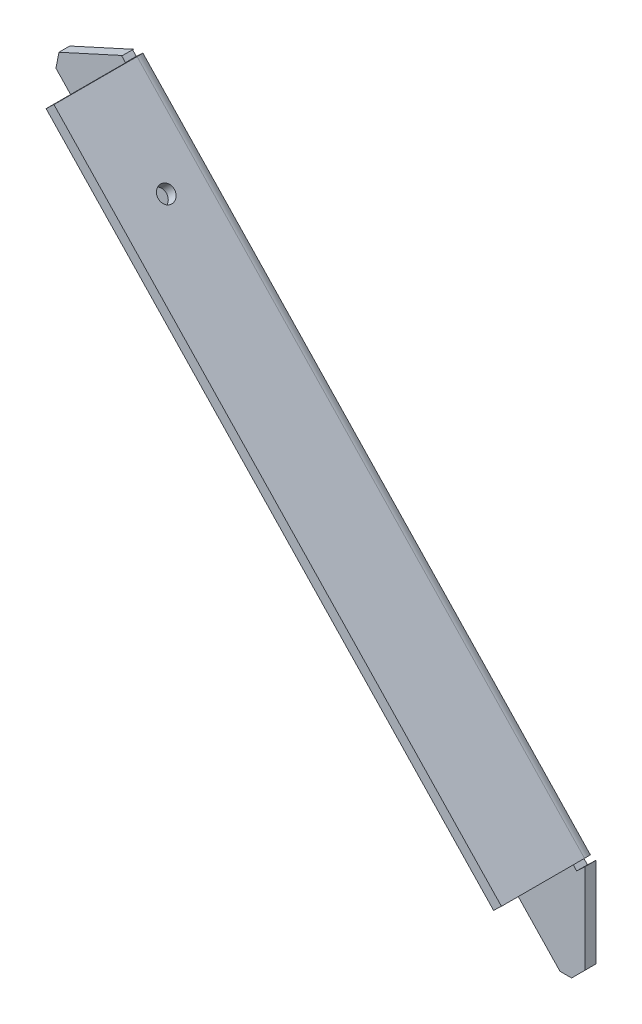
SolidWorks part; units mm, degrees
note: The reader was unsure of these and kept them because the rebuilt part matched: flange length of "Edge-Flange1".
material "ASTM A36 Steel"
ref_plane "Front Plane" through (0, 0, 0) normal (0, 0, 1) x (1, 0, 0)
ref_plane "Top Plane" through (0, 0, 0) normal (0, 1, 0) x (1, 0, 0)
ref_plane "Right Plane" through (0, 0, 0) normal (1, 0, 0) x (0, 0, -1)
sketch "Sketch1" plane through (0, 0, 0) normal (0, 0, 1) x (1, 0, 0)
  line L0 (88.2179, -94.9528) -> (-98.5073, 101.4158)
  line L1 (97.5288, -53.9528) -> (-68.2572, 120.3951)
  line L2 (88.2179, -94.9528) -> (92.5288, -94.9528)
  line L3 (-68.2572, 120.3951) -> (-97.403, 107.1127)
  line L4 (97.5288, -89.9528) -> (97.5288, -53.9528)
  line L5 (92.5288, -94.9528) -> (97.5288, -89.9528)
  line L6 (-98.5073, 101.4158) -> (-97.403, 107.1127)
base flange "Base-Flange1" sketch "Sketch1" thickness 4 reverse thickness direction no parameters "D1"=0.2
edge flange "Edge-Flange1" sketch "Sketch8" flange angle 90 flange length 35 flange position material inside bend radius 0.2 thickness 4 relief rectangular parameters "D6"=10
sketch "Sketch8" plane through (24.2756, 23.0835, 0) normal (0.7247, 0.6891, 0) x (-0.6891, 0.7247, 0)
  line L0 (-106.3044, 0) -> (134.2829, 0) construction
  line L1 (-106.3044, 0) -> (134.2829, 0)
  line L2 (-106.3044, 0) -> (-106.3044, 31)
  line L3 (-106.3044, 31) -> (134.2829, 31)
  line L4 (134.2829, 31) -> (134.2829, 0)
bend "EdgeBend1" bend radius 0.2 bend angle 90 parameters "D5"=1
sketch "Sketch9" plane through (24.2756, 23.0835, 0) normal (0.7247, 0.6891, 0) x (0, 0, -1)
  line L0 (-0.2, 134.2829) -> (-31, 134.2829) construction
  line L1 (-31, 134.2829) -> (-31, -106.3044) construction
  circle A0 centre (-13.5, 99.2829) radius 3
  dimension "D1" = 6
  dimension "D2" = 35
  dimension "D3" = 17.5
extrude "Cut-Extrude1" cut sketch "Sketch9" against normal blind 10 normal cut yes
sketch "Bend-Lines1" [suppressed] plane through (0, 0, 0) normal (0, 1, 0) x (1, 0, 0)
sketch "Bounding-Box1" [suppressed] plane through (0, 0, 0) normal (0, 1, 0) x (1, 0, 0)
sheet metal parameters "Sheet-Metal1" thickness 4 parameters "D1"=0.2
flat pattern "Flat-Pattern1" [suppressed]
sketch "Bend-Lines2" plane through (0, 0, 0) normal (0, 1, 0) x (1, 0, 0)
sketch3d "Bounding-Box2" [suppressed]
  line L0 (75.4641, 127.9742, 0) -> (-115.6286, -72.9874, 0) construction
  line L1 (100.8278, 103.8561, 0) -> (-90.2649, -97.1055, 0) construction
  line L2 (75.4641, 127.9742, 0) -> (100.8278, 103.8561, 0) construction
  line L3 (-115.6286, -72.9874, 0) -> (-90.2649, -97.1055, 0) construction
sheet metal parameters "Sheet-Metal2" thickness 4 parameters "D1"=0.2
flat pattern "Flat-Pattern1"
sketch "Bend-Lines2" plane through (0, 0, 0) normal (0, 0, 1) x (1, 0, 0)
  line L0 (95.7373, -55.6563) -> (-70.0487, 118.6916) construction
  line L1 (95.7373, -55.6563) -> (-70.0487, 118.6916) construction
sketch3d "Bounding-Box2" [suppressed]
  line L0 (-53.6834, 148.6853, 0) -> (137.4093, -52.2763, 0) construction
  line L1 (-100.8278, 103.8561, 0) -> (90.2649, -97.1055, 0) construction
  line L2 (-53.6834, 148.6853, 0) -> (-100.8278, 103.8561, 0) construction
  line L3 (137.4093, -52.2763, 0) -> (90.2649, -97.1055, 0) construction
bend of the flat pattern "Flatten-<EdgeBend1>1"
sheet metal parameters "Sheet-Metal3" thickness 4 parameters "D1"=0.2
flat pattern "Flat-Pattern1"
sketch "Bend-Lines2" plane through (0, 0, 0) normal (0, 0, 1) x (1, 0, 0)
  line L0 (95.7373, -55.6563) -> (-70.0487, 118.6916) construction
  line L1 (95.7373, -55.6563) -> (-70.0487, 118.6916) construction
sketch3d "Bounding-Box2" [suppressed]
  line L0 (-53.6834, 148.6853, 0) -> (137.4093, -52.2763, 0) construction
  line L1 (-100.8278, 103.8561, 0) -> (90.2649, -97.1055, 0) construction
  line L2 (-53.6834, 148.6853, 0) -> (-100.8278, 103.8561, 0) construction
  line L3 (137.4093, -52.2763, 0) -> (90.2649, -97.1055, 0) construction
bend of the flat pattern "Flatten-<EdgeBend1>1"
